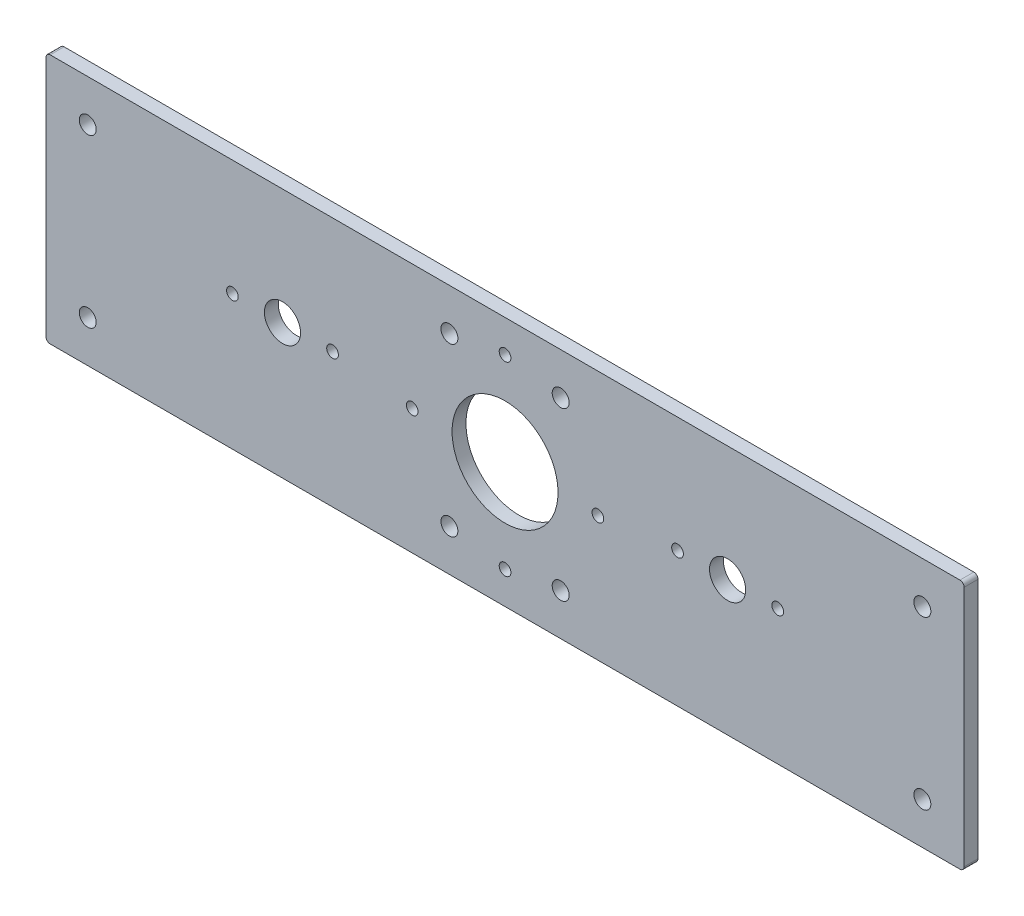
SolidWorks part; units mm, degrees
ref_plane "Front Plane" through (0, 0, 0) normal (0, 0, 1) x (1, 0, 0)
ref_plane "Top Plane" through (0, 0, 0) normal (0, 1, 0) x (1, 0, 0)
ref_plane "Right Plane" through (0, 0, 0) normal (1, 0, 0) x (0, 0, -1)
sketch "Sketch1" plane through (0, 0, 0) normal (0, 0, 1) x (1, 0, 0)
  line L0 (-165, 0) -> (165, 0) construction
  line L1 (165, -45) -> (-165, -45)
  line L2 (165, -45) -> (165, 45)
  line L3 (165, 45) -> (-165, 45)
  line L4 (-165, -45) -> (-165, 45)
  line L5 (165, -45) -> (-165, 45) construction
  line L6 (165, 45) -> (-165, -45) construction
  line L8 (0, -33.3754) -> (33.3754, 0) construction
  line L9 (0, -33.3754) -> (-33.3754, 0) construction
  line L10 (-33.3754, 0) -> (0, 33.3754) construction
  line L11 (33.3754, 0) -> (0, 33.3754) construction
  line L12 (0, -33.3754) -> (0, 33.3754) construction
  line L13 (-33.3754, 0) -> (33.3754, 0) construction
  circle A0 centre (0, 0) radius 19.05
  circle A1 centre (-33.3754, 0) radius 2.1
  circle A2 centre (33.3754, 0) radius 2.1
  circle A3 centre (0, 33.3754) radius 2.1
  circle A4 centre (0, -33.3754) radius 2.1
  point P0 (0, 0)
  dimension "D3" = 38.1
  dimension "D4" = 47.2
  dimension "D5" = 47.2
  dimension "D8" = 4.2
  dimension "D9" = 4.2
  dimension "D10" = 4.2
  dimension "D11" = 4.2
  dimension "D1" = 90
  dimension "D2" = 330
  dimension "D6" = 90
  dimension "D7" = 90
extrude "Boss-Extrude1" add sketch "Sketch1" along normal mid plane 5
sketch "Sketch2" plane through (0, 0, 2.5) normal (0, 0, 1) x (1, 0, 0)
  line L2 (-150, 45) -> (-150, -45)
  line L3 (-150, 45) -> (-150, -45) construction
  line L5 (150, -45) -> (150, 45)
  line L6 (150, -45) -> (150, 45) construction
  line L23 (165, 30) -> (-165, 30)
  line L24 (165, 30) -> (-165, 30) construction
  line L25 (0, 45) -> (0, -45) construction
  line L26 (-165, -30) -> (165, -30)
  line L27 (-165, -30) -> (165, -30) construction
  line L28 (165, 45) -> (-165, 45) construction
  line L29 (-165, -45) -> (165, -45) construction
  line L30 (-20, 45) -> (-20, -45) construction
  line L31 (20, 45) -> (20, -45) construction
  circle A0 centre (-150, 30) radius 3.05
  circle A1 centre (-150, -30) radius 3.05
  circle A2 centre (-20, 30) radius 3.05
  circle A3 centre (-20, -30) radius 3.05
  circle A4 centre (20, -30) radius 3.05
  circle A5 centre (20, 30) radius 3.05
  circle A6 centre (150, 30) radius 3.05
  circle A7 centre (150, -30) radius 3.05
  dimension "D7" = 6.1
  dimension "D8" = 6.1
  dimension "D9" = 6.1
  dimension "D10" = 6.1
  dimension "D11" = 6.1
  dimension "D12" = 6.1
  dimension "D13" = 6.1
  dimension "D14" = 6.1
  dimension "D1" = 15
  dimension "D2" = 15
  dimension "D3" = 15
  dimension "D4" = 15
  dimension "D5" = 20
  dimension "D6" = 20
extrude "Cut-Extrude1" cut sketch "Sketch2" against normal through all
sketch "Sketch3" plane through (0, 0, 2.5) normal (0, 0, 1) x (1, 0, 0)
  line L0 (0, 3.4) -> (-49.4534, 3.4) construction
  circle A0 centre (-62, 3.4) radius 2.1
  circle A1 centre (-98, 3.4) radius 2.1
  circle A2 centre (-80, 3.4) radius 6.5
  dimension "D1" = 4.2
  dimension "D2" = 4.2
  dimension "D3" = 13
  dimension "D4" = 80
  dimension "D5" = 18
  dimension "D6" = 18
  dimension "D7" = 3.4
extrude "Cut-Extrude2" cut sketch "Sketch3" against normal through all
mirror "Mirror1" about plane through (0, 0, 0) normal (1, 0, 0) of "Cut-Extrude2"
fillet "Fillet1" radius 1.5 4 edges at (-165, -45, 0) (165, -45, 0) (165, 45, 0) (-165, 45, 0)
equation "\"D4@Sketch3\"=160/2"
equation "\"D9@Sketch2\"=\"D7@Sketch2\""
equation "\"D12@Sketch2\"=\"D7@Sketch2\""
equation "\"D13@Sketch2\"=\"D7@Sketch2\""
equation "\"D8@Sketch2\"=\"D7@Sketch2\""
equation "\"D10@Sketch2\"=\"D7@Sketch2\""
equation "\"D11@Sketch2\"=\"D7@Sketch2\""
equation "\"D14@Sketch2\"=\"D7@Sketch2\""
equation "\"D9@Sketch1\"=\"D8@Sketch1\""
equation "\"D10@Sketch1\"=\"D8@Sketch1\""
equation "\"D11@Sketch1\"=\"D8@Sketch1\""
